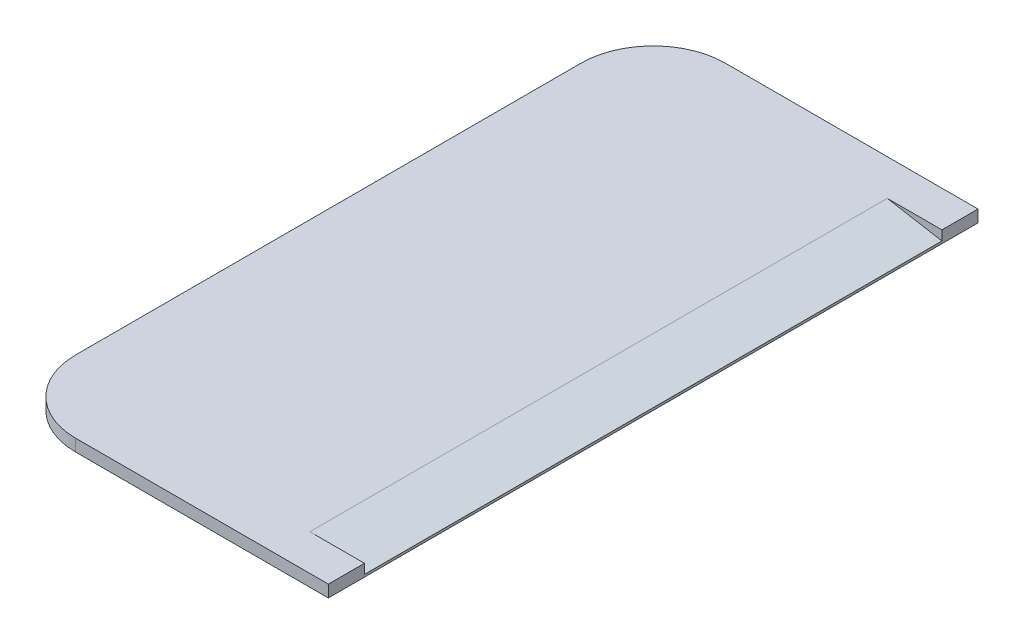
SolidWorks part; units mm, degrees
ref_plane "Front Plane" through (0, 0, 0) normal (0, 0, 1) x (1, 0, 0)
ref_plane "Top Plane" through (0, 0, 0) normal (0, 1, 0) x (1, 0, 0)
ref_plane "Right Plane" through (0, 0, 0) normal (1, 0, 0) x (0, 0, -1)
sketch "Sketch1" plane through (0, 0, 0) normal (0, 1, 0) x (1, 0, 0)
  line L1 (-7.5, -27) -> (13.5, -27)
  line L2 (-13.5, -21) -> (-13.5, 21)
  line L3 (-7.5, 27) -> (13.5, 27)
  line L4 (13.5, -27) -> (13.5, 27)
  line L5 (-13.5, -27) -> (13.5, 27) construction
  line L6 (-13.5, 27) -> (13.5, -27) construction
  arc A0 (-7.5, -27) -> (-13.5, -21) centre (-7.5, -21) cw
  arc A1 (-13.5, 21) -> (-7.5, 27) centre (-7.5, 21) cw
  point P0 (0, 0)
  dimension "D3" = 6
  dimension "D1" = 27
  dimension "D2" = 54
extrude "Boss-Extrude1" add sketch "Sketch1" along normal mid plane 1
sketch "Sketch2" plane through (0, 0, 0) normal (0, 0, 1) x (1, 0, 0)
  line L0 (13.5, -0.3) -> (8.963, 0.5)
  line L1 (13.5, 0.5) -> (13.5, -0.5) construction
  line L2 (-7.5, 0.5) -> (13.5, 0.5) construction
  line L7 (8.963, 0.5) -> (13.5, 0.5)
  line L8 (13.5, 0.5) -> (13.5, -0.3)
  dimension "D1" = 0.8
  dimension "D2" = 10
extrude "Cut-Extrude4" cut sketch "Sketch2" against normal mid plane 48
